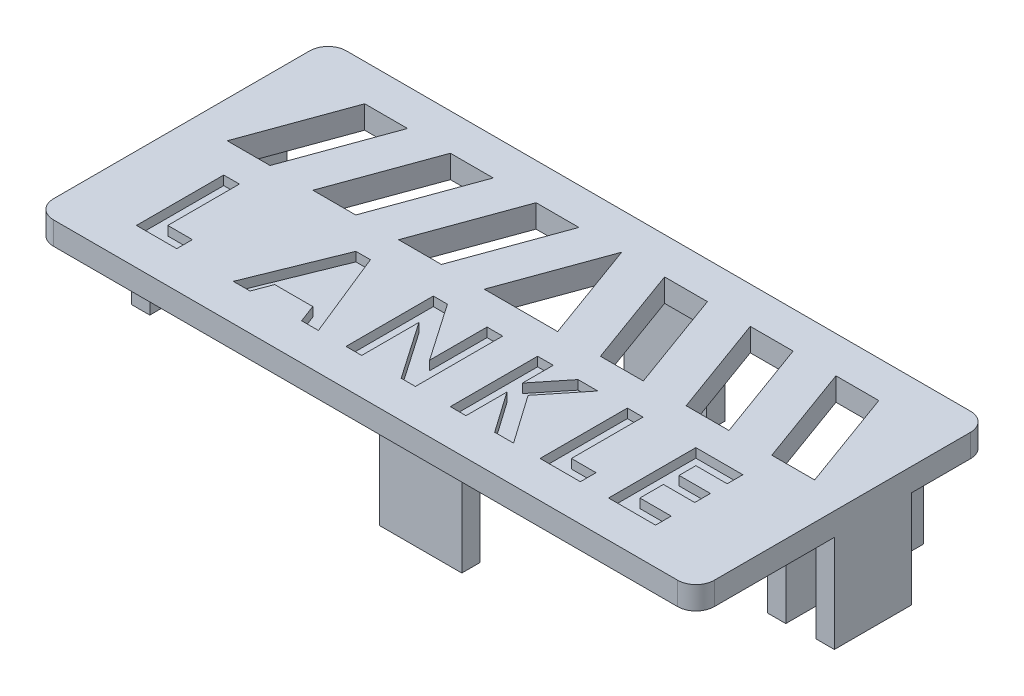
SolidWorks part; units mm, degrees
note: The reader was unsure of these and kept them because the rebuilt part matched: shared geometry of "Sketch2<3>".
ref_plane "Front" through (0, 0, 0) normal (0, 0, 1) x (1, 0, 0)
ref_plane "Top" through (0, 0, 0) normal (0, 1, 0) x (1, 0, 0)
ref_plane "Right" through (0, 0, 0) normal (1, 0, 0) x (0, 0, -1)
sketch "Sketch1" plane through (0, 0, 0) normal (0, 1, 0) x (1, 0, 0)
  line L1 (-36.05, -15.975) -> (36.05, -15.975)
  line L2 (-36.05, -15.975) -> (-36.05, 15.975)
  line L3 (-36.05, 15.975) -> (36.05, 15.975)
  line L4 (36.05, -15.975) -> (36.05, 15.975)
  line L5 (-36.05, -15.975) -> (36.05, 15.975) construction
  line L6 (-36.05, 15.975) -> (36.05, -15.975) construction
  point P0 (0, 0)
  dimension "D1" = 31.95
  dimension "D2" = 72.1
extrude "Boss-Extrude1" add sketch "Sketch1" along normal blind 2.5
fillet "Fillet1" radius 2 4 edges at (-36.05, 1.25, -15.975) (36.05, 1.25, -15.975) (36.05, 1.25, 15.975) (-36.05, 1.25, 15.975)
sketch "Sketch2" plane through (0, 0, 0) normal (0, -1, 0) x (1, 0, 0)
  line L0 (36.05, 13.975) -> (36.05, -13.975) construction
  line L1 (34.05, -7.525) -> (36.05, -7.525)
  line L2 (34.05, -7.525) -> (34.05, 0.875)
  line L3 (34.05, 0.875) -> (36.05, 0.875)
  line L4 (36.05, -7.525) -> (36.05, 0.875)
  line L5 (34.05, -7.525) -> (36.05, 0.875) construction
  line L6 (34.05, 0.875) -> (36.05, -7.525) construction
  line L7 (35.05, -7.575) -> (35.05, 0.925) construction
  line L8 (35.05, 0.925) -> (35.05, 15.975) construction
  line L9 (-34.05, 15.975) -> (34.05, 15.975) construction
  line L10 (34.05, -15.975) -> (-34.05, -15.975) construction
  line L11 (8.5, -14.725) -> (-0.5, -14.725)
  line L12 (8.5, -14.725) -> (8.5, -12.725)
  line L13 (8.5, -12.725) -> (-0.5, -12.725)
  line L14 (-0.5, -14.725) -> (-0.5, -12.725)
  line L15 (8.5, -14.725) -> (-0.5, -12.725) construction
  line L16 (8.5, -12.725) -> (-0.5, -14.725) construction
  line L17 (8.5, 11.975) -> (-0.5, 11.975)
  line L18 (8.5, 11.975) -> (8.5, 13.975)
  line L19 (8.5, 13.975) -> (-0.5, 13.975)
  line L20 (-0.5, 11.975) -> (-0.5, 13.975)
  line L21 (8.5, 11.975) -> (-0.5, 13.975) construction
  line L22 (8.5, 13.975) -> (-0.5, 11.975) construction
  line L23 (50000, 0) -> (-50000, 0) construction
  line L24 (0, -10.3523) -> (0, 10.3523) construction
  line L29 (-32.05, 7.475) -> (-32.05, -0.925)
  line L30 (-32.05, 7.475) -> (-34.05, 7.475)
  line L31 (-34.05, 7.475) -> (-34.05, -0.925)
  line L32 (-32.05, -0.925) -> (-34.05, -0.925) construction
  line L33 (-32.05, -7.475) -> (-34.05, -7.475)
  line L34 (-33.05, -0.925) -> (-33.05, -15.975) construction
  line L35 (-36.05, -13.975) -> (-36.05, 13.975) construction
  line L36 (-34.05, -0.925) -> (-34.05, -7.475)
  line L37 (-32.05, -7.475) -> (-32.05, -0.925)
  point P0 (35.05, -3.325)
  point P7 (35.05, -3.325)
  point P13 (4, -13.725)
  point P18 (4, 12.975)
  point P30 (0, 0)
  point P32 (0, 0)
  point P36 (0, 0)
  point P37 (0, 15.975)
  dimension "D1" = 2
  dimension "D2" = 8.4
  dimension "D3" = 15.05
  dimension "D4" = 8.5
  dimension "D5" = 2
  dimension "D6" = 1.25
  dimension "D7" = 2
  dimension "D8" = 0.5
  dimension "D9" = 9
  dimension "D10" = 2
extrude "Boss-Extrude2" add sketch "Sketch2" along normal blind 10.6 contours L2 L3 L4 L1 | L20 L19 L18 L17 | L13 L14 L11 L12
extrude "Boss-Extrude4" add sketch "Sketch2<3>" along normal blind 9.75 contours L31 L36 L33 L37 L29 L30
sketch "Sketch2<3>" plane through (0, 0, 0) normal (0, -1, 0) x (1, 0, 0) same geometry as "Sketch2"
sketch "Sketch4" plane through (0, 2.5, 0) normal (0, 1, 0) x (1, 0, 0)
  line L0 (-32.05, -7.475) -> (-32.05, 7.475) construction
  line L1 (-32.05, 0.975) -> (-27.3756, 0.975)
  line L3 (-28.0463, 11.975) -> (-23.3719, 11.975)
  line L7 (34.05, 15.975) -> (-34.05, 15.975) construction
  line L8 (-32.05, 0.975) -> (-36.05, 0.975) construction
  line L9 (-32.05, 0.975) -> (-28.0463, 11.975)
  line L10 (0, 0.975) -> (0, 11.975) construction
  line L11 (-23.3719, 11.975) -> (-27.3756, 0.975)
  line L12 (-22.7012, 0.975) -> (-18.6976, 11.975)
  line L13 (-18.0268, 0.975) -> (-14.0232, 11.975)
  line L14 (-13.3524, 0.975) -> (-9.3488, 11.975)
  line L15 (-8.6781, 0.975) -> (-4.6744, 11.975)
  line L16 (-30.0482, 6.475) -> (-25.3738, 6.475) construction
  line L17 (-25.3738, 6.475) -> (-20.6994, 6.475) construction
  line L18 (-20.6994, 6.475) -> (-16.025, 6.475) construction
  line L19 (-16.025, 6.475) -> (-11.3506, 6.475) construction
  line L20 (-11.3506, 6.475) -> (-6.6762, 6.475) construction
  line L21 (0, 11.975) -> (-4.0037, 0.975)
  line L22 (-6.6762, 6.475) -> (-2.0018, 6.475) construction
  line L23 (0, 11.975) -> (4.0037, 0.975)
  line L24 (8.6781, 0.975) -> (4.6744, 11.975)
  line L25 (13.3524, 0.975) -> (9.3488, 11.975)
  line L26 (18.0268, 0.975) -> (14.0232, 11.975)
  line L27 (22.7012, 0.975) -> (18.6976, 11.975)
  line L28 (23.3719, 11.975) -> (27.3756, 0.975)
  line L29 (32.05, 0.975) -> (28.0463, 11.975)
  line L30 (-4.0037, 0.975) -> (4.0037, 0.975)
  line L31 (4.6744, 11.975) -> (9.3488, 11.975)
  line L32 (8.6781, 0.975) -> (13.3524, 0.975)
  line L33 (-13.3524, 0.975) -> (-8.6781, 0.975)
  line L34 (-9.3488, 11.975) -> (-4.6744, 11.975)
  line L35 (-18.6976, 11.975) -> (-14.0232, 11.975)
  line L36 (-22.7012, 0.975) -> (-18.0268, 0.975)
  line L37 (18.0268, 0.975) -> (22.7012, 0.975)
  line L38 (14.0232, 11.975) -> (18.6976, 11.975)
  line L39 (23.3719, 11.975) -> (28.0463, 11.975)
  line L40 (27.3756, 0.975) -> (32.05, 0.975)
  line L41 (-36.05, 13.975) -> (-36.05, -13.975) construction
  line L42 (32.05, 0.975) -> (36.05, 0.975) construction
  line L43 (36.05, -13.975) -> (36.05, -0.875) construction
  point P45 (0, 0.975)
  dimension "D1" = 11
  dimension "D2" = 4
  dimension "D3" = 70
extrude "Cut-Extrude1" cut sketch "Sketch4" against normal up to vertex (2.5 mm away) up to point (-36.05, 0, -13.975)
sketch "Sketch3" plane through (0, 2.5, 0) normal (0, 1, 0) x (1, 0, 0)
  line L2 (29.55, 6.025) -> (36.05, 6.025) construction
  line L16 (32.05, -12.975) -> (-32.05, -12.975) construction
  line L17 (-34.05, -15.975) -> (34.05, -15.975) construction
  line L21 (36.05, -13.975) -> (36.05, 13.975) construction
  line L23 (-32.05, -11.975) -> (-22.05, -11.975) construction
  line L24 (-22.05, -11.975) -> (32.05, -11.975) construction
  text T0 "<b>L</b>" font "Century Gothic" height in points 36
  text T1 "<b>ANKLE</b>" font "Century Gothic" height in points 36
  point P10 (0, -12.975)
  point P11 (0, -15.975)
  dimension "D2" = 1
  dimension "D8" = 6.5
  dimension "D9" = 22
  dimension "D12" = 4
  dimension "D13" = 10
extrude "Cut-Extrude2" cut sketch "Sketch3" against normal blind 1
sketch "Sketch7" plane through (0, 2.5, 0) normal (0, 1, 0) x (1, 0, 0)
  line L15 (-12.3663, -8.3115) -> (-13.7936, -5.0049)
  line L16 (-12.3663, -8.3115) -> (-13.7936, -5.0049)
  line L17 (-13.7936, -5.0049) -> (-15.2208, -8.3115)
  line L21 (-13.7936, -5.0049) -> (-15.2208, -8.3115)
  line L22 (-15.2208, -8.3115) -> (-12.3663, -8.3115)
  line L23 (-15.2208, -8.3115) -> (-12.3663, -8.3115)
  dimension "D2" = 0
extrude "Cut-Extrude4" cut sketch "Sketch7" against normal blind 1
sketch "Sketch8" plane through (34.05, 0, 0) normal (-1, 0, 0) x (0, 0, 1)
  line L0 (-11.975, 0) -> (-0.975, 0) construction
  line L1 (4.175, -7.5) -> (-10.825, -7.5)
  line L2 (4.175, -7.5) -> (4.175, 0)
  line L3 (4.175, 0) -> (-10.825, 0)
  line L4 (-10.825, -7.5) -> (-10.825, 0)
  line L5 (4.175, -7.5) -> (-10.825, 0) construction
  line L6 (4.175, 0) -> (-10.825, -7.5) construction
  line L7 (-7.525, -10.6) -> (0.875, -10.6) construction
  point P0 (-3.325, -3.75)
  point P9 (-3.325, -10.6)
  dimension "D1" = 15
  dimension "D2" = 7.5
extrude "Boss-Extrude5" add sketch "Sketch8" along normal blind 2
equation "\"`5\"=2"
